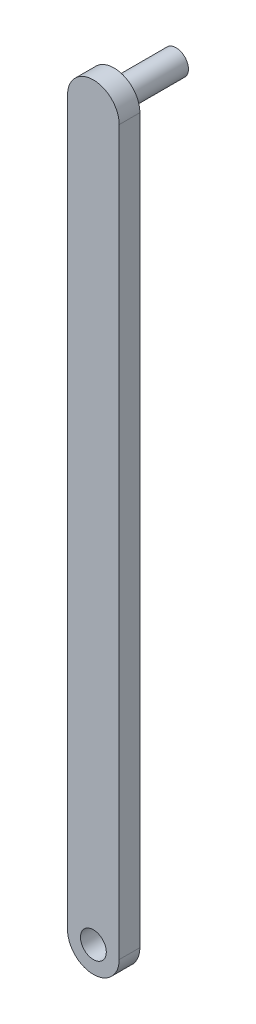
SolidWorks part; units mm, degrees
ref_plane "Front Plane" through (0, 0, 0) normal (0, 0, 1) x (1, 0, 0)
ref_plane "Top Plane" through (0, 0, 0) normal (0, 1, 0) x (1, 0, 0)
ref_plane "Right Plane" through (0, 0, 0) normal (1, 0, 0) x (0, 0, -1)
sketch "Sketch1" plane through (0, 0, 0) normal (0, 0, 1) x (1, 0, 0)
  line L0 (-3.175, 0) -> (-3.175, -88.9)
  line L1 (3.175, 0) -> (3.175, -88.9)
  arc A0 (3.175, 0) -> (-3.175, 0) centre (0, 0) ccw
  arc A1 (3.175, -88.9) -> (-3.175, -88.9) centre (0, -88.9) cw
  circle A2 centre (0, 0) radius 1.5875
  circle A3 centre (0, -88.9) radius 1.5875
  dimension "D3" = 3.175
  dimension "D4" = 3.175
  dimension "D5" = 3.175
  dimension "D1" = 3.175
  dimension "D2" = 88.9
extrude "Boss-Extrude1" add sketch "Sketch1" along normal blind 2.54
sketch "Sketch2" plane through (0, 0, 2.54) normal (0, 0, 1) x (1, 0, 0)
  circle A0 centre (0, 0) radius 1.524
  dimension "D1" = 3.048
extrude "Boss-Extrude2" add sketch "Sketch2" against normal blind 7.62 from surface starting at face at (0, -44.45, 0)
sketch "Sketch3" plane through (0, 0, 0) normal (0, 0, 1) x (1, 0, 0)
  circle A0 centre (0, 0) radius 1.5875
  dimension "D1" = 3.175
extrude "Boss-Extrude3" add sketch "Sketch3" along normal blind 2.54
